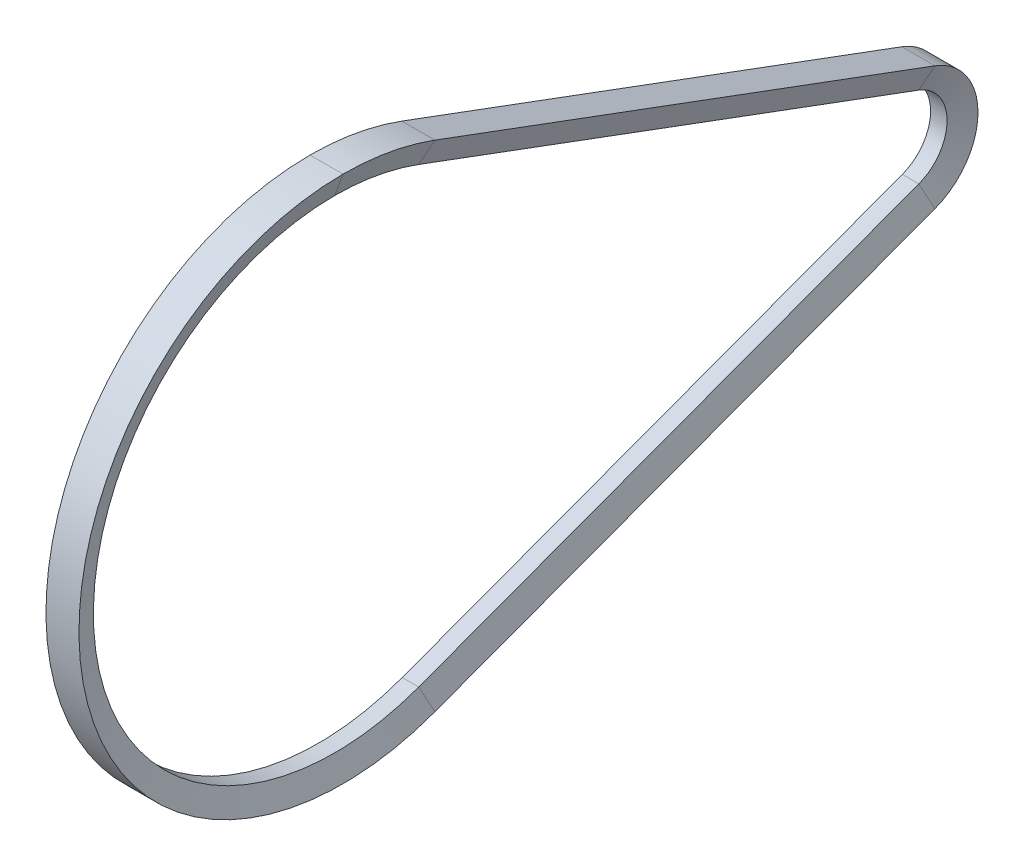
SolidWorks part; units mm, degrees
material "NEOPRENO"
ref_plane "Front" through (0, 0, 0) normal (0, 0, 1) x (1, 0, 0)
ref_plane "Top" through (0, 0, 0) normal (0, 1, 0) x (1, 0, 0)
ref_plane "Right" through (0, 0, 0) normal (1, 0, 0) x (0, 0, -1)
sketch "Croquis1" plane through (0, 0, 0) normal (1, 0, 0) x (0, 0, -1)
  line L0 (0, 0) -> (218.948, 0) construction
  line L1 (227.7879, 23.8121) -> (35.3596, 95.2484)
  line L2 (227.7879, -23.8121) -> (35.3596, -95.2484)
  arc A0 (35.3596, 95.2484) -> (35.3596, -95.2484) centre (0, 0) ccw
  arc A1 (227.7879, -23.8121) -> (227.7879, 23.8121) centre (218.948, 0) ccw
  dimension "D1" = 203.2
  dimension "D2" = 50.8
  dimension "D3" = 218.948
sketch "Croquis2" plane through (0, 0, 0) normal (0, 0, 1) x (1, 0, 0)
  line L0 (-6.35, 101.6) -> (6.35, 101.6)
  line L1 (0, 23.8121) -> (0, 95.2484) construction
  line L2 (0, -101.6) -> (0, 101.6) construction
  line L3 (6.35, 101.6) -> (3.1721, 92.8687)
  line L4 (3.1721, 92.8687) -> (-3.1721, 92.8687)
  line L5 (0, 101.6) -> (0, 92.8688) construction
  line L6 (-6.35, 101.6) -> (-3.1721, 92.8687)
  point P10 (0, 0)
  dimension "D1" = 6.35
  dimension "D2" = 8.7312
  dimension "D3" = 20
sweep "Barrer1" add profiles "Croquis2" path "Croquis1"
